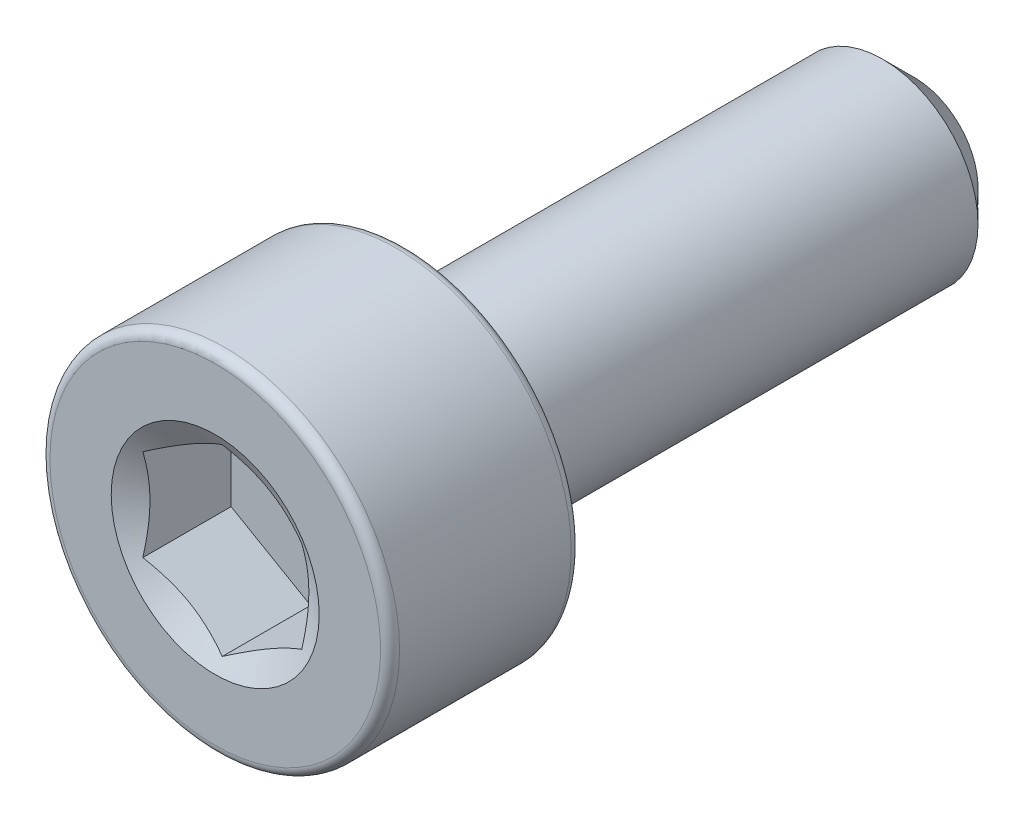
SolidWorks part; units mm, degrees
ref_plane "Front Plane" through (0, 0, 0) normal (0, 0, 1) x (1, 0, 0)
ref_plane "Top Plane" through (0, 0, 0) normal (0, 1, 0) x (1, 0, 0)
ref_plane "Right Plane" through (0, 0, 0) normal (1, 0, 0) x (0, 0, -1)
sketch "Sketch1" plane through (0, 0, 0) normal (1, 0, 0) x (0, 0, -1)
  line L0 (5.5, 0) -> (-5.5, 0) construction
  line L1 (-2.5, 2.75) -> (-2.5, -2.75) construction
  line L2 (5.5, 1.5) -> (5.5, -1.5) construction
  line L3 (5.4688, 1.5541) -> (5.7188, 1.1211) construction
  line L4 (5.6875, 1.1752) -> (5.75, 1.1752) construction
  line L5 (5.7188, 1.1211) -> (5.9688, 1.5541) construction
  line L6 (5.9688, 1.5541) -> (5.4688, 1.5541) construction
  line L7 (5.7188, 1.1752) -> (5.7188, 1.1211) construction
  line L8 (5.7188, 1.5541) -> (5.7188, 1.5) construction
  line L9 (5.9375, 1.5) -> (5.5, 1.5) construction
  point P4 (-2.5, 0)
  point P6 (-2.5, 1.25)
  point P7 (4.25, -1.5)
  point P20 (5.7188, 1.5271)
  dimension "Head Height" = 3
  dimension "Head Diameter" = 5.5
  dimension "Drive Size" = 2.5
  dimension "Length" = 8
  dimension "Thread Size" = 3
  dimension "Thread Pitch" = 0.5
  dimension "Pitch/8" = 0.0625
  dimension "Thread Note" = 1.25
sketch "Sketch2" plane through (0, 0, 0) normal (1, 0, 0) x (0, 0, -1)
  line L0 (5.5, 0) -> (5.5, 1)
  line L1 (5.5, 1.5) -> (5.5, -1.5) construction
  line L2 (5.5, 1) -> (5, 1.5)
  line L3 (5, 1.5) -> (-2.5, 1.5)
  line L4 (-2.5, 1.5) -> (-2.5, 2.6)
  line L5 (-2.65, 2.75) -> (-5.35, 2.75)
  line L6 (-5.5, 2.6) -> (-5.5, 0)
  line L7 (5.5, 0) -> (-5.5, 0) construction
  line L8 (-5.5, 0) -> (5.5, 0)
  arc A0 (-2.5, 2.6) -> (-2.65, 2.75) centre (-2.65, 2.6) ccw
  arc A1 (-5.35, 2.75) -> (-5.5, 2.6) centre (-5.35, 2.6) ccw
  point P19 (-2.5, 2.75)
  dimension "D3" = 0.15
  dimension "D1" = 0.5
  dimension "D2" = 45
revolve "Revolve1" add sketch "Sketch2" angle 360 about L0
sketch "Sketch3" plane through (0, 0, 0) normal (0, 0, 1) x (1, 0, 0)
  line L1 (-1.25, 0.7217) -> (-1.25, -0.7217)
  line L2 (-1.25, -0.7217) -> (0, -1.4434)
  line L3 (0, -1.4434) -> (1.25, -0.7217)
  line L4 (1.25, -0.7217) -> (1.25, 0.7217)
  line L5 (1.25, 0.7217) -> (0, 1.4434)
  line L6 (0, 1.4434) -> (-1.25, 0.7217)
  circle A0 centre (0, 0) radius 1.25 construction
  circle A1 centre (0, 0) radius 2.75 construction
extrude "Cut-Extrude1" cut sketch "Sketch3" against normal blind 1.5 from vertex starting at point (0, 0, 5.5)
sketch "Sketch4" plane through (0, 0, 5.5) normal (0, 0, 1) x (1, 0, 0)
  line L0 (0, 1.4434) -> (0, 1.8289) construction
  line L1 (0, 1.8289) -> (0, 2.2145) construction
  line L2 (0, 2.2145) -> (0, 2.6) construction
  circle A0 centre (0, 0) radius 1.6361
  point P12 (0, 1.6361)
extrude "Cut-Extrude2" cut sketch "Sketch4" against normal through all draft 60
split "Split1" [suppressed] bodies to split 106 112
sketch "Sketch5" [suppressed] plane through (0, 0, 0) normal (1, 0, 0) x (0, 0, -1)
  line L0 (5.6875, 1.1752) -> (5.75, 1.1752)
  line L1 (5.75, 1.1752) -> (5.9531, 1.5271)
  line L2 (5.9531, 1.5271) -> (5.4844, 1.5271)
  line L3 (5.4844, 1.5271) -> (5.6875, 1.1752)
  line L4 (5.4688, 1.5541) -> (5.7188, 1.1211) construction
sketch "Sketch6" [suppressed] plane through (0, 0, -5.5) normal (0, 0, -1) x (-1, 0, 0)
  circle A0 centre (0, 0) radius 1.5
curve "Helix/Spiral1" [suppressed] pitch 0.5 height 8.5 turns 17
sweep "Cut-Sweep1" [suppressed] cut profiles "Sketch5" path "Helix/Spiral1"
sketch "Sketch7" [suppressed] plane through (0, 0, 2.5) normal (0, 0, -1) x (-1, 0, 0)
  circle A0 centre (0, 0) radius 1.5508
  circle A1 centre (0, 0) radius 1.5 construction
  dimension "D1" = 0.0508
extrude "Boss-Extrude1" [suppressed] add sketch "Sketch7" along normal blind 1.5 draft 20 and the other way blind 0.3
equation "\"Pitch/8@Sketch1\" = \"Thread Pitch@Sketch1\" / 8"
equation "\"Thread Note@Sketch1\" = \"Thread Pitch@Sketch1\" * 2.5"
equation "\"D1@Sketch2\" = \"Thread Pitch@Sketch1\""
equation "\"D3@Sketch2\"=\"Head Height@Sketch1\"*.05"
equation "\"D1@Cut-Extrude1\" = \"Head Height@Sketch1\" * .5"
equation "\"D3@Helix/Spiral1\" = \"Length@Sketch1\" + \"Thread Pitch@Sketch1\""
equation "\"D4@Helix/Spiral1\" = \"Thread Pitch@Sketch1\""
equation "\"D2@Boss-Extrude1\" = \"Head Height@Sketch1\" * .1"
equation "\"D1\"= \"Thread Size@Sketch1\" * .4"
equation "\"D1@Boss-Extrude1\" = \"Thread Pitch@Sketch1\" * 3"
